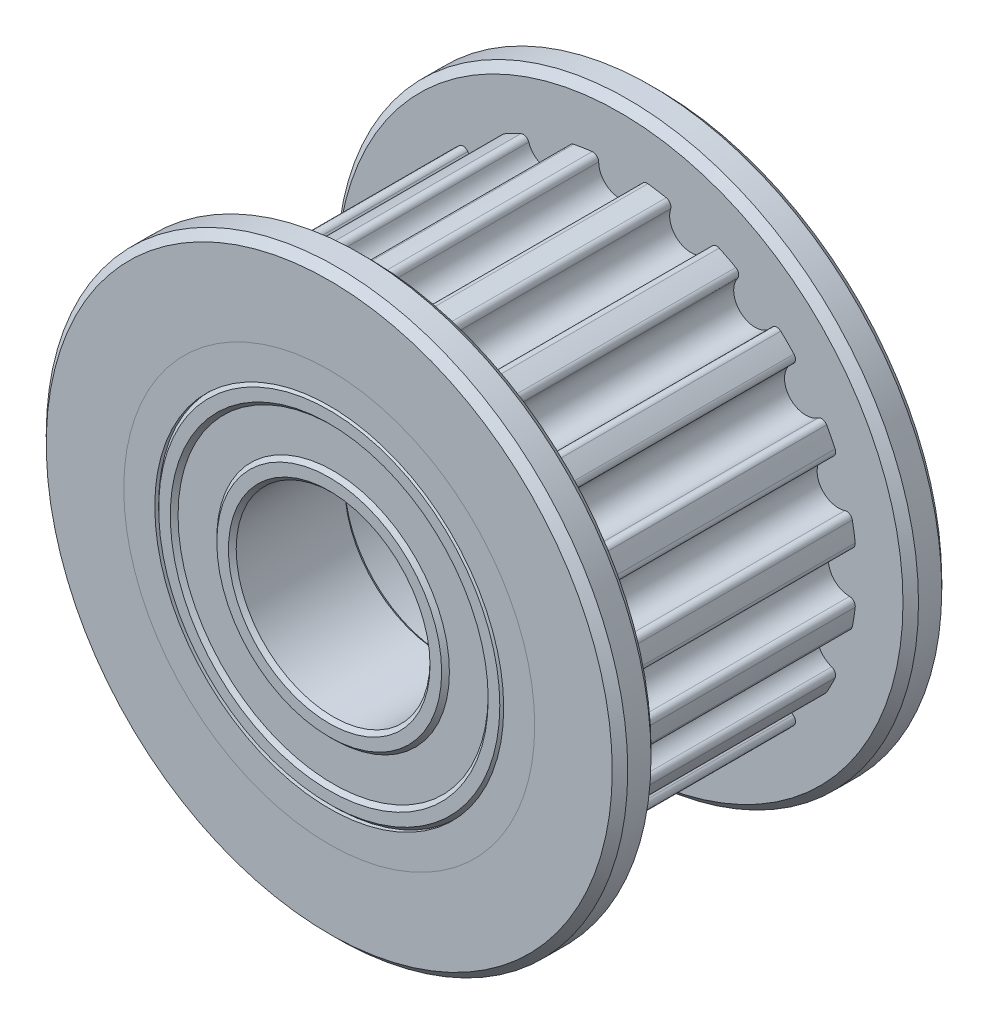
SolidWorks part; units mm, degrees
material "Alliage 6061"
ref_plane "Přední rovina" through (0, 0, 0) normal (0, 0, 1) x (1, 0, 0)
ref_plane "Horní rovina" through (0, 0, 0) normal (0, 1, 0) x (1, 0, 0)
ref_plane "Pravá rovina" through (0, 0, 0) normal (1, 0, 0) x (0, 0, -1)
sketch "Skica1" plane through (0, 0, 0) normal (0, 0, 1) x (1, 0, 0)
  circle A0 centre (0, 0) radius 5.3
  circle A1 centre (0, 0) radius 4
  circle A2 centre (0, 0) radius 7.5
  dimension "D1" = 10.6
  dimension "D2" = 8
  dimension "D3" = 15
extrude "Přidat vysunutím1" add sketch "Skica1" along normal blind 8.5 contours A0 A1 region at (-5.1501, 0, 0)
extrude "Přidat vysunutím2" add sketch "Skica1<3>" along normal blind 1 separate body contours A2 A0 region at (-7.2879, 0, 0)
sketch "Skica1<3>" plane through (0, 0, 0) normal (0, 0, 1) x (1, 0, 0) same geometry as "Skica1"
sketch "Skica2" plane through (0, 0, 1) normal (0, 0, 1) x (1, 0, 0)
  line L0 (0, 0) -> (-11.85, 0) construction
  arc A62 (-5.9201, -0.55) -> (-5.9201, 0.55) centre (-5.925, 0) ccw
  arc A63 (-5.9201, -0.55) -> (-6.0677, -0.7176) centre (-5.9188, -0.7) ccw
  arc A64 (-6.0677, 0.7176) -> (-5.9201, 0.55) centre (-5.9188, 0.7) ccw
  circle A82 centre (0, 0) radius 4.75
  circle A83 centre (0, 0) radius 6.365 construction
  circle A84 centre (0, 0) radius 5.925 construction
  arc A85 (-6.0677, 0.7176) -> (-5.9925, 1.1926) centre (0, 0) cw
  arc A86 (-5.9925, -1.1926) -> (-6.0677, -0.7176) centre (0, 0) cw
  circle A87 centre (0, 0) radius 7.5 construction
  arc A88 (-5.9925, -1.1926) -> (-5.8003, -1.3063) centre (-5.8454, -1.1633) ccw
  arc A89 (-5.4604, -2.3525) -> (-5.8003, -1.3063) centre (-5.635, -1.8309) ccw
  arc A90 (-5.4604, -2.3525) -> (-5.549, -2.5575) centre (-5.4128, -2.4947) ccw
  arc A91 (-5.3307, -2.986) -> (-5.549, -2.5575) centre (0, 0) cw
  arc A92 (-5.3307, -2.986) -> (-5.1127, -3.0348) centre (-5.1998, -2.9127) ccw
  arc A93 (-4.4662, -3.9247) -> (-5.1127, -3.0348) centre (-4.7934, -3.4826) ccw
  arc A94 (-4.4662, -3.9247) -> (-4.4871, -4.1471) centre (-4.3769, -4.0452) ccw
  arc A95 (-4.1471, -4.4871) -> (-4.4871, -4.1471) centre (0, 0) cw
  arc A96 (-4.1471, -4.4871) -> (-3.9247, -4.4662) centre (-4.0452, -4.3769) ccw
  arc A97 (-3.0348, -5.1127) -> (-3.9247, -4.4662) centre (-3.4826, -4.7934) ccw
  arc A98 (-3.0348, -5.1127) -> (-2.986, -5.3307) centre (-2.9127, -5.1998) ccw
  arc A99 (-2.5575, -5.549) -> (-2.986, -5.3307) centre (0, 0) cw
  arc A100 (-2.5575, -5.549) -> (-2.3525, -5.4604) centre (-2.4947, -5.4128) ccw
  arc A101 (-1.3063, -5.8003) -> (-2.3525, -5.4604) centre (-1.8309, -5.635) ccw
  arc A102 (-1.3063, -5.8003) -> (-1.1926, -5.9925) centre (-1.1633, -5.8454) ccw
  arc A103 (-0.7176, -6.0677) -> (-1.1926, -5.9925) centre (0, 0) cw
  arc A104 (-0.7176, -6.0677) -> (-0.55, -5.9201) centre (-0.7, -5.9188) ccw
  arc A105 (0.55, -5.9201) -> (-0.55, -5.9201) centre (0, -5.925) ccw
  arc A106 (0.55, -5.9201) -> (0.7176, -6.0677) centre (0.7, -5.9188) ccw
  arc A107 (1.1926, -5.9925) -> (0.7176, -6.0677) centre (0, 0) cw
  arc A108 (1.1926, -5.9925) -> (1.3063, -5.8003) centre (1.1633, -5.8454) ccw
  arc A109 (2.3525, -5.4604) -> (1.3063, -5.8003) centre (1.8309, -5.635) ccw
  arc A110 (2.3525, -5.4604) -> (2.5575, -5.549) centre (2.4947, -5.4128) ccw
  arc A111 (2.986, -5.3307) -> (2.5575, -5.549) centre (0, 0) cw
  arc A112 (2.986, -5.3307) -> (3.0348, -5.1127) centre (2.9127, -5.1998) ccw
  arc A113 (3.9247, -4.4662) -> (3.0348, -5.1127) centre (3.4826, -4.7934) ccw
  arc A114 (3.9247, -4.4662) -> (4.1471, -4.4871) centre (4.0452, -4.3769) ccw
  arc A115 (4.4871, -4.1471) -> (4.1471, -4.4871) centre (0, 0) cw
  arc A116 (4.4871, -4.1471) -> (4.4662, -3.9247) centre (4.3769, -4.0452) ccw
  arc A117 (5.1127, -3.0348) -> (4.4662, -3.9247) centre (4.7934, -3.4826) ccw
  arc A118 (5.1127, -3.0348) -> (5.3307, -2.986) centre (5.1998, -2.9127) ccw
  arc A119 (5.549, -2.5575) -> (5.3307, -2.986) centre (0, 0) cw
  arc A120 (5.549, -2.5575) -> (5.4604, -2.3525) centre (5.4128, -2.4947) ccw
  arc A121 (5.8003, -1.3063) -> (5.4604, -2.3525) centre (5.635, -1.8309) ccw
  arc A122 (5.8003, -1.3063) -> (5.9925, -1.1926) centre (5.8454, -1.1633) ccw
  arc A123 (6.0677, -0.7176) -> (5.9925, -1.1926) centre (0, 0) cw
  arc A124 (6.0677, -0.7176) -> (5.9201, -0.55) centre (5.9188, -0.7) ccw
  arc A125 (5.9201, 0.55) -> (5.9201, -0.55) centre (5.925, 0) ccw
  arc A126 (5.9201, 0.55) -> (6.0677, 0.7176) centre (5.9188, 0.7) ccw
  arc A127 (5.9925, 1.1926) -> (6.0677, 0.7176) centre (0, 0) cw
  arc A128 (5.9925, 1.1926) -> (5.8003, 1.3063) centre (5.8454, 1.1633) ccw
  arc A129 (5.4604, 2.3525) -> (5.8003, 1.3063) centre (5.635, 1.8309) ccw
  arc A130 (5.4604, 2.3525) -> (5.549, 2.5575) centre (5.4128, 2.4947) ccw
  arc A131 (5.3307, 2.986) -> (5.549, 2.5575) centre (0, 0) cw
  arc A132 (5.3307, 2.986) -> (5.1127, 3.0348) centre (5.1998, 2.9127) ccw
  arc A133 (4.4662, 3.9247) -> (5.1127, 3.0348) centre (4.7934, 3.4826) ccw
  arc A134 (4.4662, 3.9247) -> (4.4871, 4.1471) centre (4.3769, 4.0452) ccw
  arc A135 (4.1471, 4.4871) -> (4.4871, 4.1471) centre (0, 0) cw
  arc A136 (4.1471, 4.4871) -> (3.9247, 4.4662) centre (4.0452, 4.3769) ccw
  arc A137 (3.0348, 5.1127) -> (3.9247, 4.4662) centre (3.4826, 4.7934) ccw
  arc A138 (3.0348, 5.1127) -> (2.986, 5.3307) centre (2.9127, 5.1998) ccw
  arc A139 (2.5575, 5.549) -> (2.986, 5.3307) centre (0, 0) cw
  arc A140 (2.5575, 5.549) -> (2.3525, 5.4604) centre (2.4947, 5.4128) ccw
  arc A141 (1.3063, 5.8003) -> (2.3525, 5.4604) centre (1.8309, 5.635) ccw
  arc A142 (1.3063, 5.8003) -> (1.1926, 5.9925) centre (1.1633, 5.8454) ccw
  circle A143 centre (0, 0) radius 6.11 construction
  arc A144 (0.7176, 6.0677) -> (1.1926, 5.9925) centre (0, 0) cw
  arc A145 (0.7176, 6.0677) -> (0.55, 5.9201) centre (0.7, 5.9188) ccw
  arc A146 (-0.55, 5.9201) -> (0.55, 5.9201) centre (0, 5.925) ccw
  arc A147 (-0.55, 5.9201) -> (-0.7176, 6.0677) centre (-0.7, 5.9188) ccw
  arc A148 (-1.1926, 5.9925) -> (-0.7176, 6.0677) centre (0, 0) cw
  arc A149 (-1.1926, 5.9925) -> (-1.3063, 5.8003) centre (-1.1633, 5.8454) ccw
  arc A150 (-2.3525, 5.4604) -> (-1.3063, 5.8003) centre (-1.8309, 5.635) ccw
  arc A151 (-2.3525, 5.4604) -> (-2.5575, 5.549) centre (-2.4947, 5.4128) ccw
  arc A152 (-2.986, 5.3307) -> (-2.5575, 5.549) centre (0, 0) cw
  arc A153 (-2.986, 5.3307) -> (-3.0348, 5.1127) centre (-2.9127, 5.1998) ccw
  arc A154 (-3.9247, 4.4662) -> (-3.0348, 5.1127) centre (-3.4826, 4.7934) ccw
  arc A155 (-3.9247, 4.4662) -> (-4.1471, 4.4871) centre (-4.0452, 4.3769) ccw
  arc A156 (-4.4871, 4.1471) -> (-4.1471, 4.4871) centre (0, 0) cw
  arc A157 (-4.4871, 4.1471) -> (-4.4662, 3.9247) centre (-4.3769, 4.0452) ccw
  arc A158 (-5.1127, 3.0348) -> (-4.4662, 3.9247) centre (-4.7934, 3.4826) ccw
  arc A159 (-5.1127, 3.0348) -> (-5.3307, 2.986) centre (-5.1998, 2.9127) ccw
  arc A160 (-5.549, 2.5575) -> (-5.3307, 2.986) centre (0, 0) cw
  arc A161 (-5.549, 2.5575) -> (-5.4604, 2.3525) centre (-5.4128, 2.4947) ccw
  arc A162 (-5.8003, 1.3063) -> (-5.4604, 2.3525) centre (-5.635, 1.8309) ccw
  arc A163 (-5.8003, 1.3063) -> (-5.9925, 1.1926) centre (-5.8454, 1.1633) ccw
  point P171 (0, 0)
  dimension "D1" = 12.73
  dimension "D2" = 12.22
  dimension "D3" = 11.85
  dimension "D4" = 0.55
  dimension "D5" = 0.15
  dimension "D6" = 0.15
  dimension "D8" = 9.5
  dimension "D7" = 20
extrude "Přidat vysunutím5" add sketch "Skica2" along normal blind 6.5 separate body
sketch "Skica4" plane through (0, 0, 7.5) normal (0, 0, 1) x (1, 0, 0)
  circle A0 centre (0, 0) radius 7.5
  circle A1 centre (0, 0) radius 5.3
  circle A2 centre (0, 0) radius 7.5 construction
extrude "Přidat vysunutím6" add sketch "Skica4" along normal blind 1 separate body
sketch "Skica5" plane through (0, 0, 8.5) normal (0, 0, 1) x (1, 0, 0)
  circle A0 centre (0, 0) radius 4.5
  dimension "D1" = 9
sketch "Skica6" plane through (0, 0, 0) normal (0, 0, -1) x (-1, 0, 0)
  circle A0 centre (0, 0) radius 4.5
  dimension "D1" = 9
extrude "Odebrat vysunutím3" cut sketch "Skica5" against normal blind 3
extrude "Odebrat vysunutím4" cut sketch "Skica6" against normal blind 3
chamfer "Zkosení1" distance 0.2 angle 45 2 edges at (7.5, 0, 1) (7.5, 0, 0)
chamfer "Zkosení2" distance 0.2 angle 45 2 edges at (7.5, 0, 7.5) (7.5, 0, 8.5)
sketch "Skica7" plane through (0, 0, 3) normal (0, 0, -1) x (-1, 0, 0)
  circle A0 centre (0, 0) radius 4.5
  circle A1 centre (0, 0) radius 2.5
  circle A2 centre (0, 0) radius 3
  circle A3 centre (0, 0) radius 4
  circle M1 centre (0, 0) radius 4
  circle M2 centre (0, 0) radius 4.5
extrude "Přidat vysunutím7" add sketch "Skica7" along normal blind 3 separate body contours M2 M1 | A2 A1 region at (4.3727, 0, 3) region at (2.9151, 0, 3)
extrude "Přidat vysunutím8" add sketch "Skica7<3>" along normal blind 2.8 from offset 0.1 separate body contours A2 M1 region at (3.8869, 0, 3)
sketch "Skica7<3>" plane through (0, 0, 3) normal (0, 0, -1) x (-1, 0, 0) same geometry as "Skica7"
chamfer "Zkosení3" distance 0.1 angle 45 2 edges at (-4, 0, 0) (-4.5, 0, 0)
chamfer "Zkosení4" distance 0.1 angle 45 2 edges at (-3, 0, 0) (-2.5, 0, 0)
sketch "Skica8" plane through (0, 0, 5.5) normal (0, 0, 1) x (1, 0, 0)
  circle A0 centre (0, 0) radius 4.5
  circle A1 centre (0, 0) radius 2.5
  circle A2 centre (0, 0) radius 3
  circle A3 centre (0, 0) radius 4
  circle M1 centre (0, 0) radius 4
  circle M2 centre (0, 0) radius 4.5
  dimension "D1" = 9
  dimension "D2" = 8
  dimension "D3" = 6
  dimension "D4" = 5
extrude "Přidat vysunutím9" add sketch "Skica8" along normal blind 3 separate body contours M2 M1 | A2 A1 region at (-4.3727, 0, 5.5) region at (-2.9151, 0, 5.5)
extrude "Přidat vysunutím10" add sketch "Skica8<3>" along normal blind 2.8 from offset 0.1 separate body contours A2 M1 region at (-3.8869, 0, 5.5)
sketch "Skica8<3>" plane through (0, 0, 5.5) normal (0, 0, 1) x (1, 0, 0) same geometry as "Skica8"
chamfer "Zkosení5" distance 0.1 angle 45 2 edges at (4, 0, 8.5) (4.5, 0, 8.5)
chamfer "Zkosení6" distance 0.1 angle 45 2 edges at (3, 0, 8.5) (2.5, 0, 8.5)
chamfer "Zkosení7" distance 0.1 angle 45 2 edges at (3, 0, 5.5) (2.5, 0, 5.5)
chamfer "Zkosení8" distance 0.1 angle 45 2 edges at (4.5, 0, 5.5) (4, 0, 5.5)
chamfer "Zkosení10" distance 0.1 angle 45 2 edges at (-3, 0, 3) (-2.5, 0, 3)
chamfer "Zkosení12" distance 0.1 angle 45 2 edges at (-4, 0, 3) (-4.5, 0, 3)
